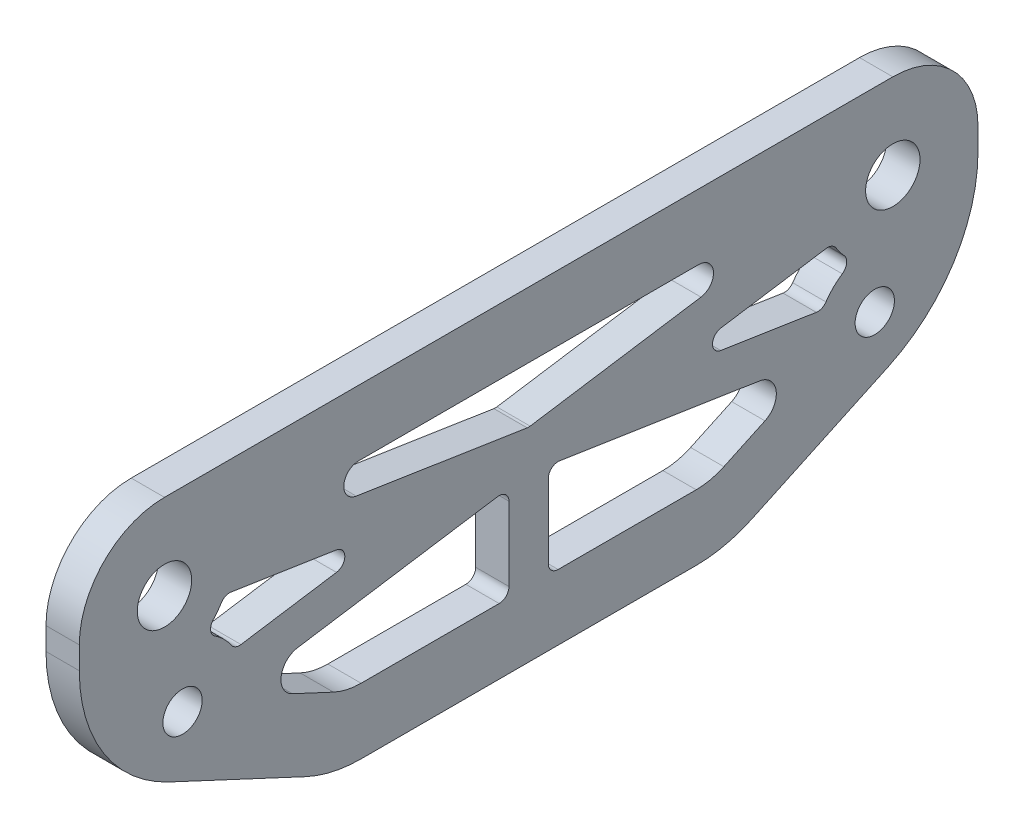
SolidWorks part; units mm, degrees
ref_plane "Front Plane" through (0, 0, 0) normal (0, 0, 1) x (1, 0, 0)
ref_plane "Top Plane" through (0, 0, 0) normal (0, 1, 0) x (1, 0, 0)
ref_plane "Right Plane" through (0, 0, 0) normal (1, 0, 0) x (0, 0, -1)
sketch "Sketch1" plane through (0, 0, 0) normal (1, 0, 0) x (0, 0, -1)
  line L0 (15, 12.3931) -> (27.786, 12.3931)
  line L1 (-15, -12.3931) -> (15, -12.3931)
  line L3 (-15, 12.3931) -> (15, 12.3931)
  line L5 (-15, -12.3931) -> (15, 12.3931) construction
  line L6 (-15, 12.3931) -> (15, -12.3931) construction
  line L8 (0, 12.3931) -> (0, -12.3931) construction
  line L10 (-15, 12.3931) -> (-27.786, 12.3931)
  line L11 (22.286, 124.8696) -> (22.286, -102.5304) construction
  line L13 (34.286, 5.8931) -> (34.286, 4.1845)
  line L14 (27.4122, -6.6052) -> (15, -12.3931)
  line L16 (-34.286, 5.8931) -> (-34.286, 4.1845)
  line L17 (-27.4122, -6.6052) -> (-15, -12.3931)
  arc A0 (27.786, 12.3931) -> (34.286, 5.8931) centre (27.786, 5.8931) cw
  circle A1 centre (27.786, 5.8931) radius 5.5 construction
  circle A2 centre (-27.786, 5.8931) radius 5.5 construction
  arc A3 (-27.786, 12.3931) -> (-34.286, 5.8931) centre (-27.786, 5.8931) ccw
  arc A4 (34.286, 4.1845) -> (27.4122, -6.6052) centre (22.3809, 4.1845) cw
  circle A5 centre (27.786, 5.8931) radius 2.075
  arc A6 (-34.286, 4.1845) -> (-27.4122, -6.6052) centre (-22.3809, 4.1845) ccw
  circle A9 centre (-27.786, 5.8931) radius 2.075
  circle A11 centre (26.4083, -2.4557) radius 1.5
  circle A12 centre (-26.4083, -2.4557) radius 1.5
  point P0 (0, 0)
  point P28 (0, 0)
  dimension "D1" = 11
  dimension "D2" = 1
  dimension "D3" = 4.15
  dimension "D4" = 3
  dimension "D6" = 25
  dimension "D7" = 30
extrude "Boss-Extrude1" add sketch "Sketch1" along normal blind 2.54
fillet "Fillet1" radius 10 2 edges at (1.27, -12.3931, -15) (1.27, -12.3931, 15)
sketch "Sketch2" plane through (0, 0, 0) normal (1, 0, 0) x (0, 0, -1)
  line L0 (-27.786, 5.8931) -> (26.4083, -2.4557) construction
  line L10 (-27.786, -2.6679) -> (27.786, 5.8931)
  line L11 (-27.786, 5.8931) -> (26.4083, -2.4557)
  line L12 (-28.0144, 4.4106) -> (26.18, -3.9382)
  line L13 (-27.5576, 7.3756) -> (26.6367, -0.9731)
  line L14 (-28.0144, 4.4106) -> (-27.5576, 7.3756)
  line L15 (26.18, -3.9382) -> (26.6367, -0.9731)
  line L16 (-12.7831, -7.3931) -> (12.7831, -7.3931)
  line L17 (14.8961, -6.9246) -> (25.2991, -2.0737)
  line L18 (29.286, 4.1845) -> (29.286, 5.8931)
  line L19 (27.786, 7.3931) -> (-27.786, 7.3931)
  line L20 (-29.286, 5.8931) -> (-29.286, 4.1845)
  line L21 (-25.2991, -2.0737) -> (-14.8961, -6.9246)
  line L22 (-12.7831, -7.3931) -> (12.7831, -7.3931)
  line L23 (14.8961, -6.9246) -> (25.2991, -2.0737)
  line L24 (29.286, 4.1845) -> (29.286, 5.8931)
  line L25 (27.786, 7.3931) -> (-27.786, 7.3931)
  line L26 (-29.286, 5.8931) -> (-29.286, 4.1845)
  line L27 (-25.2991, -2.0737) -> (-14.8961, -6.9246)
  line L28 (-27.5576, -4.1504) -> (28.0144, 4.4106)
  line L29 (-28.0144, -1.1854) -> (27.5576, 7.3756)
  line L30 (-27.5576, -4.1504) -> (-28.0144, -1.1854)
  line L31 (28.0144, 4.4106) -> (27.5576, 7.3756)
  line L32 (0, -7.3931) -> (0, 7.3931) construction
  line L33 (0, 1.6126) -> (0, -7.3931)
  line L34 (-1.5, 1.6126) -> (-1.5, -7.3931)
  line L35 (1.5, 1.6126) -> (1.5, -7.3931)
  line L36 (-1.5, 1.6126) -> (1.5, 1.6126)
  line L37 (-1.5, -7.3931) -> (1.5, -7.3931)
  arc A0 (-17.6263, -2.6205) -> (-18.0318, -5.4624) centre (-17.3979, -4.103) ccw
  arc A1 (17.6263, -2.6205) -> (18.0318, -5.4624) centre (17.3979, -4.103) cw
  circle A2 centre (-26.4083, -2.4557) radius 4.5
  circle A3 centre (-26.4083, -2.4557) radius 4.5
  circle A5 centre (26.4083, -2.4557) radius 4.5
  circle A6 centre (26.4083, -2.4557) radius 4.5
  circle A11 centre (-27.786, 5.8931) radius 5.075
  arc A12 (12.7831, -7.3931) -> (14.8961, -6.9246) centre (12.7831, -2.3931) ccw
  arc A13 (25.2991, -2.0737) -> (29.286, 4.1845) centre (22.3809, 4.1845) ccw
  arc A14 (29.286, 5.8931) -> (27.786, 7.3931) centre (27.786, 5.8931) ccw
  arc A15 (-27.786, 7.3931) -> (-29.286, 5.8931) centre (-27.786, 5.8931) ccw
  arc A16 (-29.286, 4.1845) -> (-25.2991, -2.0737) centre (-22.3809, 4.1845) ccw
  arc A17 (-14.8961, -6.9246) -> (-12.7831, -7.3931) centre (-12.7831, -2.3931) ccw
  arc A18 (12.7831, -7.3931) -> (14.8961, -6.9246) centre (12.7831, -2.3931) ccw
  arc A19 (25.2991, -2.0737) -> (29.286, 4.1845) centre (22.3809, 4.1845) ccw
  arc A20 (29.286, 5.8931) -> (27.786, 7.3931) centre (27.786, 5.8931) ccw
  arc A21 (-27.786, 7.3931) -> (-29.286, 5.8931) centre (-27.786, 5.8931) ccw
  arc A22 (-29.286, 4.1845) -> (-25.2991, -2.0737) centre (-22.3809, 4.1845) ccw
  arc A23 (-14.8961, -6.9246) -> (-12.7831, -7.3931) centre (-12.7831, -2.3931) ccw
  circle A24 centre (-27.786, 5.8931) radius 5.075
  circle A26 centre (27.786, 5.8931) radius 5.075
  circle A27 centre (27.786, 5.8931) radius 5.075
  arc A32 (12.9795, 7.3931) -> (13.1508, 5.1562) centre (12.9795, 6.2681) cw
  arc A33 (-12.9795, 7.3931) -> (-13.1508, 5.1562) centre (-12.9795, 6.2681) ccw
  dimension "D11" = 3
  dimension "D12" = 1.125
  dimension "D2" = 1.5
  dimension "D1" = 5
  dimension "D3" = 3
  dimension "D4" = 3
  dimension "D6" = 1.5
  dimension "D7" = 1.5
  dimension "D8" = 1.5
  dimension "D9" = 1.5
  dimension "D13" = 1.5
  dimension "D14" = 1.5
  dimension "D15" = 3
extrude "Cut-Extrude2" cut sketch "Sketch2" along normal through all contours A24 A3 L29 L12 | A27 L28 L13 A6 | L25 A33 L13 L29 A32 | A1 L12 L35 L22 | L28 A0 L22 L34 region at (0, 1.6682, 19.033) region at (0, -4.2501, 9.0264) region at (0, 5.7355, 0) region at (0, -4.2501, -9.0264) region at (0, 1.6682, -19.033)
fillet "Fillet2" radius 0.75 13 edges at (1.27, -7.3931, -1.5) (1.27, 3.6724, -23.2226) (1.27, 1.6126, -9.8518) (1.27, 3.6724, 23.2226) (1.27, 3.1303, 0) (1.27, -0.1362, -1.5) (1.27, -7.3931, 1.5) (1.27, -0.1362, 1.5) (1.27, 1.6126, 9.8518) (1.27, -0.3272, -22.4435) (1.27, 1.7617, -24.8386) (1.27, -0.3272, 22.4435) (1.27, 1.7617, 24.8386)
